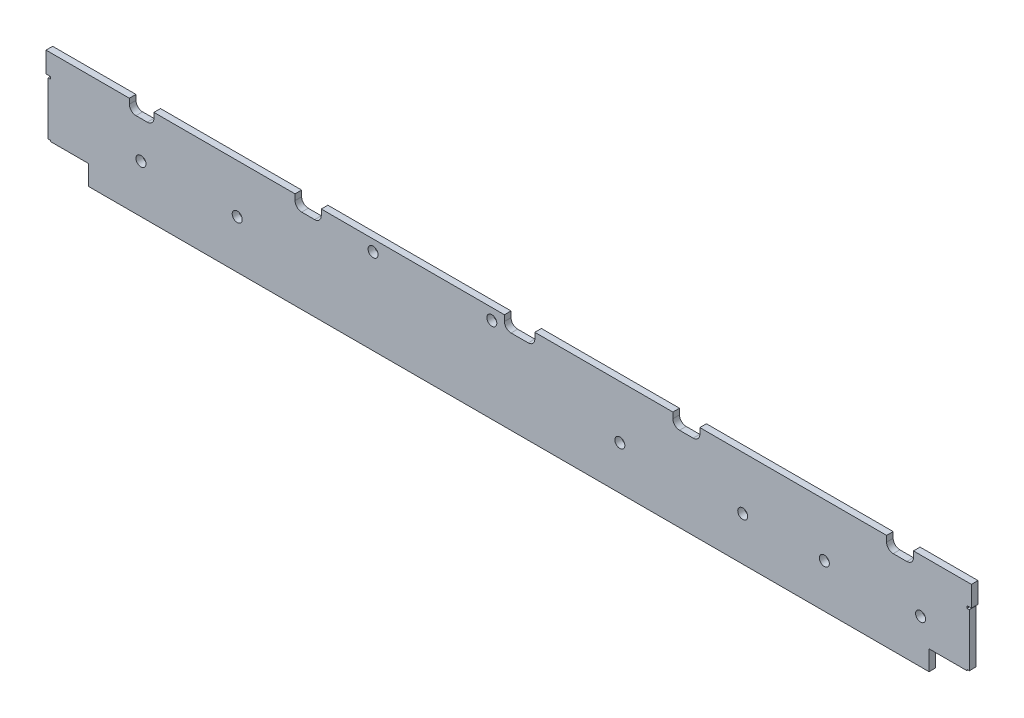
SolidWorks part; units mm, degrees
material "PP Film"
ref_plane "X-Y Datum" through (0, 0, 0) normal (0, 0, 1) x (1, 0, 0)
ref_plane "X-Z Datum" through (0, 0, 0) normal (0, 1, 0) x (1, 0, 0)
ref_plane "Y-Z Datum" through (0, 0, 0) normal (1, 0, 0) x (0, 0, -1)
sketch "Sketch2" plane through (0, 0, 0) normal (0, 0, 1) x (1, 0, 0)
  line L0 (-174.4992, -157.216) -> (269.7668, -157.216)
  line L20 (249.4468, -203.714) -> (249.4468, -194.181)
  line L21 (249.4468, -194.181) -> (267.6238, -194.181)
  line L22 (267.6238, -194.181) -> (267.6238, -193.665)
  line L23 (267.6238, -193.665) -> (268.7668, -193.665)
  line L24 (268.7668, -193.665) -> (268.7668, -168.265)
  line L25 (268.7668, -168.265) -> (267.6238, -168.265)
  line L26 (267.6238, -168.265) -> (267.6238, -167.122)
  line L27 (267.6238, -167.122) -> (269.7668, -167.122)
  line L28 (269.7668, -167.122) -> (269.7668, -157.216)
  line L29 (269.7668, -157.216) -> (241.9429, -157.216)
  line L30 (-174.4992, -157.216) -> (-174.4992, -167.122)
  line L31 (-174.4992, -167.122) -> (-172.3562, -167.122)
  line L32 (-172.3562, -167.122) -> (-172.3562, -168.265)
  line L33 (-172.3562, -168.265) -> (-173.4992, -168.265)
  line L34 (-173.4992, -168.265) -> (-173.4992, -193.665)
  line L35 (-173.4992, -193.665) -> (-172.3562, -193.665)
  line L36 (-172.3562, -193.665) -> (-172.3562, -194.181)
  line L37 (-172.3562, -194.181) -> (-154.1792, -194.181)
  line L38 (-154.1792, -194.181) -> (-154.1792, -203.714)
  line L39 (-154.1792, -203.714) -> (249.4468, -203.714)
  line L41 (249.4468, -194.181) -> (267.6238, -194.181)
  line L42 (267.6238, -194.181) -> (267.6238, -193.665)
  line L43 (267.6238, -193.665) -> (268.7668, -193.665)
  line L44 (268.7668, -193.665) -> (268.7668, -168.265)
  line L45 (268.7668, -168.265) -> (267.6238, -168.265)
  line L46 (267.6238, -168.265) -> (267.6238, -167.122)
  line L47 (267.6238, -167.122) -> (269.7668, -167.122)
  line L48 (269.7668, -167.122) -> (269.7668, -157.216)
  line L50 (-174.4992, -157.216) -> (-174.4992, -167.122)
  line L51 (-174.4992, -167.122) -> (-172.3562, -167.122)
  line L52 (-172.3562, -167.122) -> (-172.3562, -168.265)
  line L53 (-172.3562, -168.265) -> (-173.4992, -168.265)
  line L54 (-173.4992, -168.265) -> (-173.4992, -193.665)
  line L55 (-173.4992, -193.665) -> (-172.3562, -193.665)
  line L56 (-172.3562, -193.665) -> (-172.3562, -194.181)
  line L57 (-172.3562, -194.181) -> (-154.1792, -194.181)
  line L58 (-154.1792, -194.181) -> (-154.1792, -203.714)
  line L59 (-154.1792, -203.714) -> (249.4468, -203.714)
  line L196 (249.4468, -203.714) -> (249.4468, -194.181)
  line L611 (-134.4822, -157.216) -> (-174.4992, -157.216)
  line L612 (-125.8659, -162.8707) -> (-131.3072, -162.8707)
  line L613 (-125.8659, -162.8707) -> (-131.3072, -162.8707)
  line L614 (-134.4822, -159.6957) -> (-134.4822, -157.216)
  line L615 (-134.4822, -159.6957) -> (-134.4822, -157.216)
  line L616 (241.9429, -157.216) -> (241.9429, -160.0289)
  line L617 (241.9429, -157.216) -> (241.9429, -160.0289)
  line L618 (238.7679, -163.2039) -> (232.2288, -163.2039)
  line L619 (238.7679, -163.2039) -> (232.2288, -163.2039)
  line L620 (229.0538, -160.0289) -> (229.0538, -157.216)
  line L621 (229.0538, -160.0289) -> (229.0538, -157.216)
  line L622 (229.0538, -157.216) -> (139.3917, -157.216)
  line L623 (229.0538, -157.216) -> (139.3917, -157.216)
  line L624 (139.3917, -157.216) -> (139.3917, -160.0289)
  line L625 (139.3917, -157.216) -> (139.3917, -160.0289)
  line L626 (136.2167, -163.2039) -> (129.6343, -163.2039)
  line L627 (136.2167, -163.2039) -> (129.6343, -163.2039)
  line L628 (126.4593, -160.0289) -> (126.4593, -157.216)
  line L629 (126.4593, -160.0289) -> (126.4593, -157.216)
  line L630 (126.4593, -157.216) -> (60.1739, -157.216)
  line L631 (126.4593, -157.216) -> (60.1739, -157.216)
  line L632 (60.1739, -157.216) -> (60.1739, -160.0289)
  line L633 (60.1739, -157.216) -> (60.1739, -160.0289)
  line L634 (56.9989, -163.2039) -> (48.7597, -163.2039)
  line L635 (56.9989, -163.2039) -> (48.7597, -163.2039)
  line L636 (45.5847, -160.0289) -> (45.5847, -157.216)
  line L637 (45.5847, -160.0289) -> (45.5847, -157.216)
  line L638 (45.5847, -157.216) -> (-42.3503, -157.216)
  line L639 (45.5847, -157.216) -> (-42.3503, -157.216)
  line L640 (-42.3503, -157.216) -> (-42.3503, -160.0289)
  line L641 (-42.3503, -157.216) -> (-42.3503, -160.0289)
  line L642 (-45.5253, -163.2039) -> (-51.766, -163.2039)
  line L643 (-45.5253, -163.2039) -> (-51.766, -163.2039)
  line L644 (-54.941, -160.0289) -> (-54.941, -157.216)
  line L645 (-54.941, -160.0289) -> (-54.941, -157.216)
  line L646 (-54.941, -157.216) -> (-122.6909, -157.216)
  line L647 (-54.941, -157.216) -> (-122.6909, -157.216)
  line L648 (-122.6909, -157.216) -> (-122.6909, -159.6957)
  line L649 (-122.6909, -157.216) -> (-122.6909, -159.6957)
  arc A20 (-125.8659, -162.8707) -> (-122.6909, -159.6957) centre (-125.8659, -159.6957) ccw
  arc A21 (-125.8659, -162.8707) -> (-122.6909, -159.6957) centre (-125.8659, -159.6957) ccw
  arc A22 (-134.4822, -159.6957) -> (-131.3072, -162.8707) centre (-131.3072, -159.6957) ccw
  arc A23 (-134.4822, -159.6957) -> (-131.3072, -162.8707) centre (-131.3072, -159.6957) ccw
  arc A24 (238.7679, -163.2039) -> (241.9429, -160.0289) centre (238.7679, -160.0289) ccw
  arc A25 (238.7679, -163.2039) -> (241.9429, -160.0289) centre (238.7679, -160.0289) ccw
  arc A26 (229.0538, -160.0289) -> (232.2288, -163.2039) centre (232.2288, -160.0289) ccw
  arc A27 (229.0538, -160.0289) -> (232.2288, -163.2039) centre (232.2288, -160.0289) ccw
  arc A28 (136.2167, -163.2039) -> (139.3917, -160.0289) centre (136.2167, -160.0289) ccw
  arc A29 (136.2167, -163.2039) -> (139.3917, -160.0289) centre (136.2167, -160.0289) ccw
  arc A30 (126.4593, -160.0289) -> (129.6343, -163.2039) centre (129.6343, -160.0289) ccw
  arc A31 (126.4593, -160.0289) -> (129.6343, -163.2039) centre (129.6343, -160.0289) ccw
  arc A32 (56.9989, -163.2039) -> (60.1739, -160.0289) centre (56.9989, -160.0289) ccw
  arc A33 (56.9989, -163.2039) -> (60.1739, -160.0289) centre (56.9989, -160.0289) ccw
  arc A34 (45.5847, -160.0289) -> (48.7597, -163.2039) centre (48.7597, -160.0289) ccw
  arc A35 (45.5847, -160.0289) -> (48.7597, -163.2039) centre (48.7597, -160.0289) ccw
  arc A36 (-45.5253, -163.2039) -> (-42.3503, -160.0289) centre (-45.5253, -160.0289) ccw
  arc A37 (-45.5253, -163.2039) -> (-42.3503, -160.0289) centre (-45.5253, -160.0289) ccw
  arc A38 (-54.941, -160.0289) -> (-51.766, -163.2039) centre (-51.766, -160.0289) ccw
  arc A39 (-54.941, -160.0289) -> (-51.766, -163.2039) centre (-51.766, -160.0289) ccw
  dimension "D1" = 0
extrude "Boss-Extrude1" add sketch "Sketch2" along normal blind 3.175 contours L58 L59 L196 L41 L42 L43 L44 L45 L46 L47 L48 L50 L51 L52 L53 L54 L55 L56 L57 region at (47.5065, -180.4774, 0)
sketch "Sketch3" plane through (0, 0, 0) normal (0, 0, -1) x (-1, 0, 0)
  circle A0 centre (-245.3703, -182.706) radius 2
  circle A1 centre (-199.1703, -182.706) radius 2
  circle A2 centre (-159.9918, -182.714) radius 2
  circle A3 centre (-100.9918, -182.714) radius 2
  circle A4 centre (-39.5223, -162.606) radius 2
  circle A5 centre (17.4777, -162.606) radius 2
  circle A6 centre (82.7027, -180.606) radius 2
  circle A7 centre (128.9027, -180.606) radius 2
  point P0 (17.4777, -162.606)
  point P2 (-39.5223, -162.606)
  point P4 (128.9027, -180.606)
  point P6 (82.7027, -180.606)
  point P8 (-100.9918, -182.714)
  point P10 (-245.3703, -182.706)
  point P12 (-199.1703, -182.706)
  point P14 (-159.9918, -182.714)
  dimension "D1" = 4
extrude "Cut-Extrude1" cut sketch "Sketch3" against normal through all both and the other way through all
hole_wizard "M4 Clearance Hole1" positions "Sketch6" profile "Sketch5" hole size "M4" standard "ANSI Metric" end condition up to next
sketch "Sketch6" plane through (0, 0, 0) normal (0, 0, -1) x (-1, 0, 0)
  point P0 (-245.3703, -182.706)
  point P3 (-199.1703, -182.706)
  point P6 (-159.9918, -182.714)
  point P9 (-100.9918, -182.714)
  point P12 (-39.5223, -162.606)
  point P15 (17.4777, -162.606)
  point P18 (82.7027, -180.606)
  point P21 (128.9027, -180.606)
sketch "Sketch5" plane through (245.3703, -182.706, 0) normal (1, 0, 0) x (0, 1, 0)
  line L0 (0, 0) -> (0, 3.175)
  line L1 (0, 3.175) -> (2.4, 3.175)
  line L2 (2.4, 3.175) -> (2.4, 0)
  line L5 (2.4, 0) -> (0, 0)
  line L11 (0, -6.35) -> (0, 107.95) construction
  dimension "Thru Hole Dia." = 4.8
  dimension "Thru Hole Depth" = 3.175
